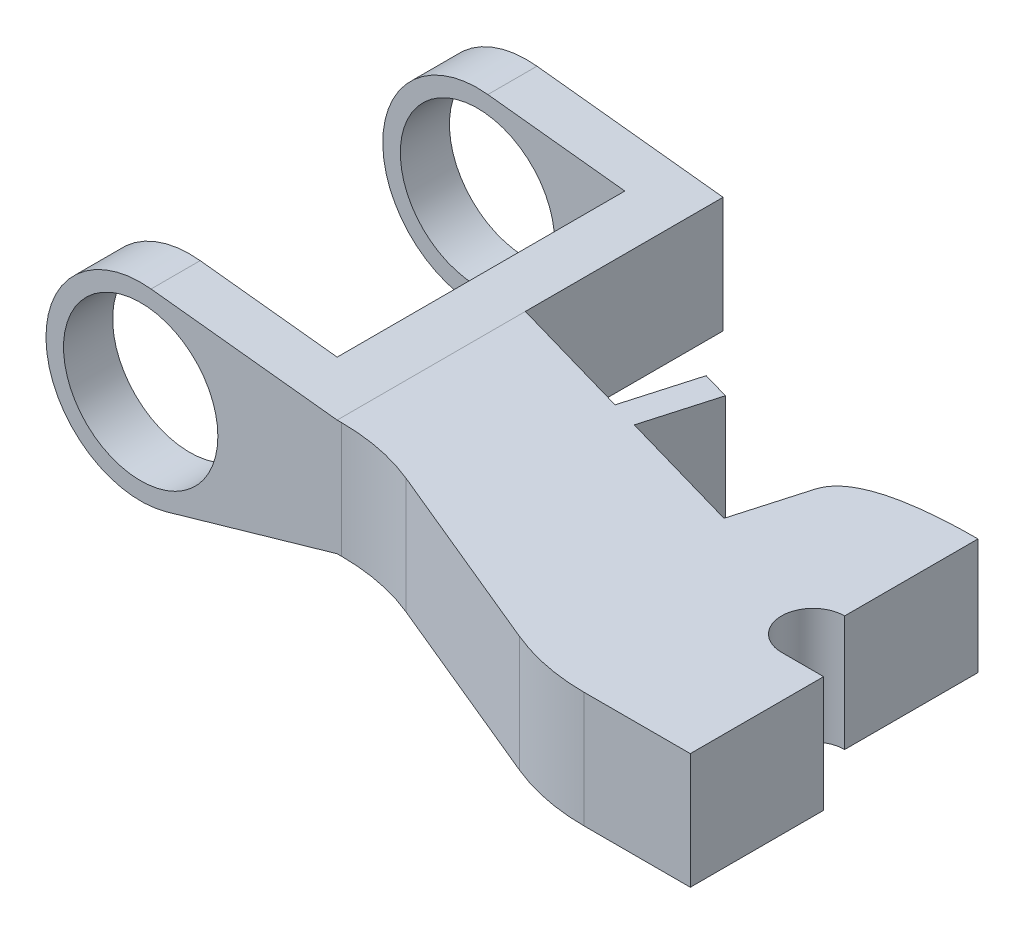
SolidWorks part; units mm, degrees
ref_plane "Спереди" through (0, 0, 0) normal (0, 0, 1) x (1, 0, 0)
ref_plane "Сверху" through (0, 0, 0) normal (0, 1, 0) x (1, 0, 0)
ref_plane "Справа" through (0, 0, 0) normal (1, 0, 0) x (0, 0, -1)
sketch "Эскиз8" plane through (0, 0, 0) normal (0, 1, 0) x (1, 0, 0)
  line L0 (-31.6673, 77.5) -> (-62.0836, 77.5) construction
  line L1 (-85, 43.6529) -> (-6, 21) construction
  line L2 (-106, 13.5) -> (-92.5, 13.5)
  line L3 (-92.5, 13.5) -> (-92.5, 6.5)
  line L4 (-92.5, 6.5) -> (-119.5, 6.5)
  line L6 (-119.5, 6.5) -> (-119.5, 13.5)
  line L7 (-119.5, 13.5) -> (-106, 13.5)
  line L8 (-117, 28.0456) -> (-95, 28.0456) construction
  line L31 (-92.5, 61.5) -> (-119.5, 61.5)
  line L32 (-119.5, 61.5) -> (-119.5, 54.5)
  line L33 (-119.5, 54.5) -> (-92.5, 54.5)
  line L34 (-92.5, 54.5) -> (-92.5, 61.5)
  line L37 (-62.0836, 77.5) -> (-62.0836, 61.5) construction
  line L38 (-62.0836, 61.5) -> (-92.5, 61.5) construction
  line L39 (-11.6673, -9.5) -> (-52.0836, -9.5) construction
  line L44 (-52.0836, -9.5) -> (-52.0836, 6.5) construction
  line L45 (-42.6378, 23.1833) -> (-38.3121, 21.943)
  line L46 (-17.6673, 16.0231) -> (-17.6673, 18.5) construction
  line L47 (-52.0836, 6.5) -> (-92.5, 6.5) construction
  line L48 (-106, 28.0456) -> (-85, 28.0456) construction
  line L52 (-92.5, 54.5) -> (-85, 54.5)
  line L53 (-85, 54.5) -> (-85, 13.5)
  line L54 (-85, 13.5) -> (-92.5, 13.5)
  line L56 (-6, 21) -> (-6, 28) construction
  line L59 (-78, 61.5) -> (-78, 63.0226)
  line L60 (-35.418, 32.0362) -> (-39.7436, 33.2766)
  line L61 (-78, 61.5) -> (-78, 33.3233)
  line L64 (-11.6673, 9.5) -> (-17.6673, 9.5)
  line L65 (-17.6673, 37.5) -> (-17.6673, 18.5) construction
  line L67 (-38.3121, 21.943) -> (-35.418, 32.0362)
  line L68 (-41.1218, 28.4703) -> (-42.6378, 23.1833) construction
  line L69 (-60.3189, 28.2533) -> (-57.4247, 38.3465) construction
  line L70 (-39.7436, 33.2766) -> (-41.1218, 28.4703)
  line L71 (-41.1218, 28.4703) -> (-36.7961, 27.2299)
  line L72 (-42.6378, 23.1833) -> (-78, 33.3233)
  line L79 (-38.3121, 21.943) -> (-17.6673, 16.0231) construction
  line L82 (-35.418, 32.0362) -> (-33.8512, 37.5) construction
  line L83 (-57.665, 38.4155) -> (-61.5101, 39.518)
  line L84 (-57.4247, 38.3465) -> (-57.665, 38.4155)
  line L85 (-57.4247, 38.3465) -> (-57.1844, 38.2776)
  line L86 (-57.1844, 38.2776) -> (-60.0786, 28.1844)
  line L87 (-61.5101, 39.518) -> (-62.8883, 34.7117)
  line L88 (-62.8883, 34.7117) -> (-58.5626, 33.4713)
  line L89 (-57.1844, 38.2776) -> (-53.3394, 37.1751)
  line L90 (-53.3394, 37.1751) -> (-56.2335, 27.0818)
  line L91 (-62.8883, 34.7117) -> (-64.4043, 29.4248) construction
  line L92 (-33.8512, 37.5) -> (-17.6673, 37.5) construction
  circle A1 centre (-106, 28.0456) radius 11
  circle A6 centre (-106, 28.0456) radius 13.5
  arc A8 (-17.6673, 18.5) -> (-17.6673, 9.5) centre (-17.6673, 14) ccw
  spline S0 degree 3 poles (-31.6673, 77.5) (-62.0836, 77.5) (-62.0836, 61.5) (-92.5, 61.5) knots 0 0 0 0 1 1 1 1
  spline S1 degree 3 poles (-11.6673, -9.5) (-52.0836, -9.5) (-52.0836, 6.5) (-92.5, 6.5) knots 0 0 0 0 1 1 1 1
  spline S3 degree 2 poles (-35.418, 32.0362) (-33.8512, 37.5) (-17.6673, 37.5) knots 0 0 0 1 1 1
  point P48 (-60.3189, 28.2533)
sketch "Эскиз10" plane through (0, 0, 0) normal (0, 1, 0) x (1, 0, 0)
  line L0 (-34.4146, 72.312) -> (-60.5171, 61.5) construction
  line L1 (-52.0836, -1.5) -> (-71.3973, 6.5)
  line L2 (-92.5, 61.5) -> (-60.5171, 61.5)
  line L3 (-52.0836, 6.5) -> (-52.0836, -1.5) construction
  line L4 (-78, 33.3233) -> (-78, 61.5)
  line L5 (-92.5, 6.5) -> (-11.6673, 6.5) construction
  line L7 (-52.0836, -1.5) -> (-32.7699, -9.5)
  line L8 (-11.6673, -9.5) -> (-32.7699, -9.5)
  line L9 (-52.0836, -1.5) -> (-11.6673, -1.5) construction
  line L10 (-92.5, 6.5) -> (-71.3973, 6.5)
  line L13 (-92.5, 54.5) -> (-85, 54.5)
  line L14 (-85, 54.5) -> (-85, 13.5)
  line L15 (-85, 13.5) -> (-92.5, 13.5)
  line L17 (-17.6673, 9.5) -> (-11.6673, 9.5)
  line L18 (-11.6673, 9.5) -> (-11.6673, -9.5)
  line L19 (-17.6673, 18.5) -> (-17.6673, 37.5)
  line L20 (-35.418, 32.0362) -> (-33.8512, 37.5) construction
  line L22 (-33.8512, 37.5) -> (-17.6673, 37.5) construction
  line L24 (-35.418, 32.0362) -> (-38.3121, 21.943)
  line L25 (-38.3121, 21.943) -> (-56.2335, 27.0818)
  line L27 (-60.0786, 28.1844) -> (-57.1844, 38.2776)
  line L28 (-57.1844, 38.2776) -> (-53.3394, 37.1751)
  line L29 (-53.3394, 37.1751) -> (-56.2335, 27.0818)
  line L30 (-60.0786, 28.1844) -> (-78, 33.3233)
  line L32 (-92.5, 61.5) -> (-119.5, 61.5)
  line L34 (-92.5, 54.5) -> (-119.5, 54.5)
  line L35 (-119.5, 61.5) -> (-119.5, 54.5)
  line L36 (-92.5, 13.5) -> (-119.5, 13.5)
  line L38 (-92.5, 6.5) -> (-119.5, 6.5)
  line L39 (-119.5, 13.5) -> (-119.5, 6.5)
  arc A1 (-17.6673, 18.5) -> (-17.6673, 9.5) centre (-17.6673, 14) ccw
  arc A2 (-17.6673, 18.5) -> (-17.6673, 9.5) centre (-17.6673, 14) ccw construction
  spline S4 degree 2 poles (-35.418, 32.0362) (-33.8512, 37.5) (-17.6673, 37.5) knots 0 0 0 1 1 1
extrude "Бобышка-Вытянуть1" add sketch "Эскиз10" along normal mid plane 27 separate body contours S4 L24 L25 L29 L28 L27 L30 L4 L2 L32 L35 L34 L13 L14 L15 L36 L39 L38 L10 L1 L7 L8 L18 L17 A1 L19 region at (-57.4823, 0, -19.3085)
sketch "Эскиз11" plane through (0, 0, 0) normal (0, 0, 1) x (1, 0, 0)
  line L10 (-11.6673, -6) -> (-11.6673, 10.5)
  line L16 (-106, 0) -> (-11.6673, 0) construction
  line L21 (-11.6673, -6) -> (0, -6) construction
  line L31 (-11.6673, 10.5) -> (-78, 10.5)
  line L50 (-119.5, 13.5) -> (-11.6673, 13.5)
  line L51 (-119.5, 13.5) -> (-119.5, -13.5)
  line L52 (-119.5, -13.5) -> (-11.6673, -13.5)
  line L53 (-11.6673, 13.5) -> (-11.6673, -13.5)
  line L55 (-78, 10.5) -> (-78, -6)
  line L56 (-78, -6) -> (-11.6673, -6)
  line L57 (-78, -6) -> (-102.2714, -12.9749)
  line L58 (-78, 10.5) -> (-104.5232, 13.419)
  circle A2 centre (-106, 0) radius 11
  circle A5 centre (-106, 0) radius 13.5
  point P4 (0, 0)
  point P11 (0, 0)
  point P13 (0, 0)
  point P19 (0, 0)
  point P21 (0, 0)
  point P22 (0, 0)
extrude "Вырез-Вытянуть1" cut sketch "Эскиз11" against normal through all both and the other way through all contours A2 | A5 L51 L52 | A5 L50 L51 | L52 L53 | L50 L53 region at (-51.7306, -9.9565, 0) region at (-52.0379, 12.0853, 0) region at (-116.4845, -10.4845, 0) region at (-116.4845, 10.4845, 0) region at (-106, 0, 0)
sketch "Эскиз12" plane through (-62.9818, 0, -18.0597) normal (-0.9613, 0, -0.2756) x (-0.2756, 0, 0.9613)
  line L0 (-21.0327, 10.5) -> (-21.0327, -6) construction
  line L1 (-21.0327, 2.25) -> (-18.5327, 2.25) construction
  circle A0 centre (-18.5327, 2.25) radius 2.5
extrude "Бобышка-Вытянуть2" add sketch "Эскиз12" along normal blind 4.5
sketch "Эскиз13" plane through (-41.2153, 0, -11.8183) normal (-0.9613, 0, -0.2756) x (-0.2756, 0, 0.9613)
  line L0 (-21.0327, 2.25) -> (-18.5327, 2.25) construction
  line L1 (-21.0327, 10.5) -> (-21.0327, -6) construction
  circle A0 centre (-18.5327, 2.25) radius 2.5
extrude "Бобышка-Вытянуть3" add sketch "Эскиз13" along normal blind 4.5
fillet "Скругление1" radius 30 2 edges at (-32.7699, 2.25, 9.5) (-71.3973, 2.25, -6.5)
